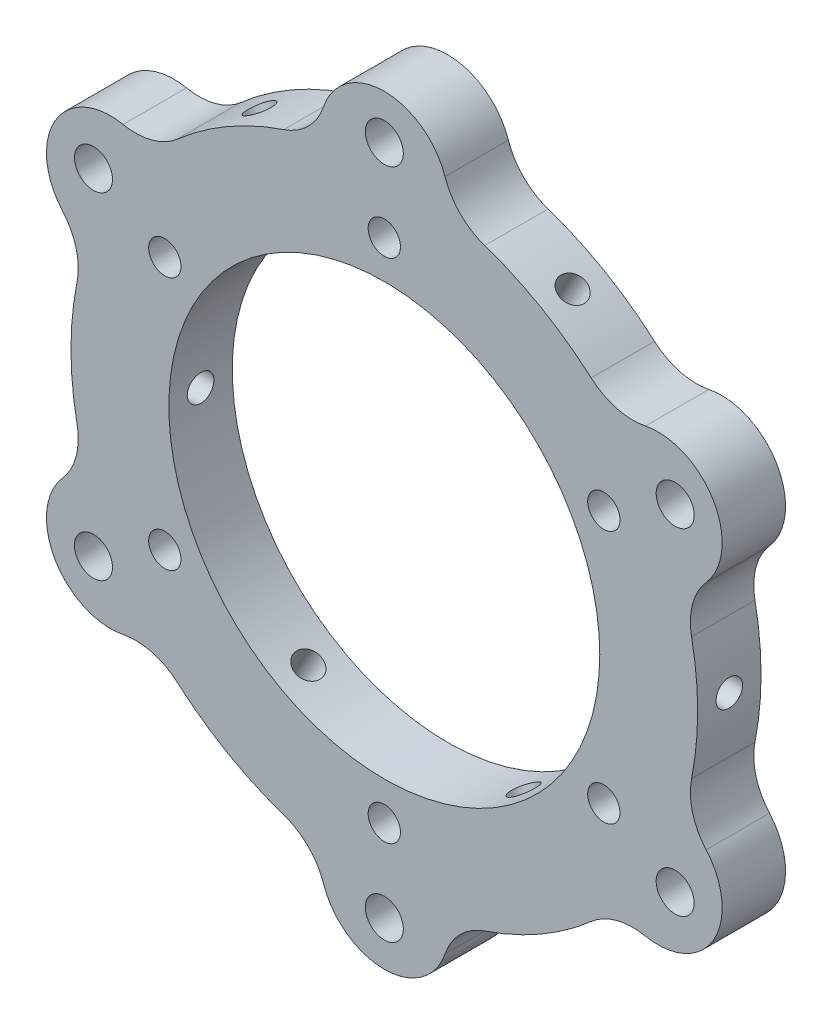
SolidWorks part; units mm, degrees
material "6063-T6"
ref_plane "Front Plane" through (0, 0, 0) normal (0, 0, 1) x (1, 0, 0)
ref_plane "Top Plane" through (0, 0, 0) normal (0, 1, 0) x (1, 0, 0)
ref_plane "Right Plane" through (0, 0, 0) normal (1, 0, 0) x (0, 0, -1)
sketch "Sketch5" plane through (0, 0, 0) normal (0, 1, 0) x (1, 0, 0)
  line L0 (0, -16.5008) -> (0, 15.0181) construction
ref_plane "Plane1" through (0, 0, 0) normal (-0.5, 0.866, 0) x (0, 0, -1)
sketch "Sketch2" plane through (0, 0, 0) normal (0, 0, 1) x (1, 0, 0)
  line L0 (0, 0) -> (0, 53) construction
  line L1 (0, 0) -> (0, 40) construction
  line L2 (0, 0) -> (0, 53) construction
  circle A0 centre (0, 0) radius 34
  circle A1 centre (0, 0) radius 60
  circle A2 centre (0, 53) radius 3
  circle A3 centre (45.8993, 26.5) radius 3
  circle A4 centre (45.8993, -26.5) radius 3
  circle A5 centre (0, -53) radius 3
  circle A6 centre (-45.8993, -26.5) radius 3
  circle A7 centre (-45.8993, 26.5) radius 3
  circle A11 centre (0, 0) radius 53 construction
  circle A12 centre (0, 40) radius 2.55
  circle A13 centre (34.641, 20) radius 2.55
  circle A14 centre (34.641, -20) radius 2.55
  circle A15 centre (0, -40) radius 2.55
  circle A16 centre (-34.641, -20) radius 2.55
  circle A17 centre (-34.641, 20) radius 2.55
  circle A18 centre (0, 0) radius 46.95 construction
  arc A19 (-15.849, 46.8413) -> (15.849, 46.8413) centre (0, 0) ccw
  arc A21 (-9.5776, 53.1206) -> (9.5776, 53.1206) centre (0, 49.8933) cw
  arc A22 (9.5776, 53.1206) -> (15.849, 46.8413) centre (19.0541, 56.3138) ccw
  circle A23 centre (0, 0) radius 49.45 construction
  arc A24 (-9.5776, 53.1206) -> (-15.849, 46.8413) centre (-19.0541, 56.3138) cw
  arc A25 (41.215, 34.8547) -> (50.7926, 18.2658) centre (43.2088, 24.9466) cw
  arc A26 (41.215, 34.8547) -> (32.6413, 37.1463) centre (39.2422, 44.6582) cw
  arc A27 (50.7926, 18.2658) -> (48.4903, 9.695) centre (58.2962, 11.6556) ccw
  arc A28 (50.7926, -18.2658) -> (41.215, -34.8547) centre (43.2088, -24.9466) cw
  arc A29 (50.7926, -18.2658) -> (48.4903, -9.695) centre (58.2962, -11.6556) cw
  arc A30 (41.215, -34.8547) -> (32.6413, -37.1463) centre (39.2422, -44.6582) ccw
  arc A31 (9.5776, -53.1206) -> (-9.5776, -53.1206) centre (0, -49.8933) cw
  arc A32 (9.5776, -53.1206) -> (15.849, -46.8413) centre (19.0541, -56.3138) cw
  arc A33 (-9.5776, -53.1206) -> (-15.849, -46.8413) centre (-19.0541, -56.3138) ccw
  arc A34 (-41.215, -34.8547) -> (-50.7926, -18.2658) centre (-43.2088, -24.9466) cw
  arc A35 (-41.215, -34.8547) -> (-32.6413, -37.1463) centre (-39.2422, -44.6582) cw
  arc A36 (-50.7926, -18.2658) -> (-48.4903, -9.695) centre (-58.2962, -11.6556) ccw
  arc A37 (-50.7926, 18.2658) -> (-41.215, 34.8547) centre (-43.2088, 24.9466) cw
  arc A38 (-50.7926, 18.2658) -> (-48.4903, 9.695) centre (-58.2962, 11.6556) cw
  arc A39 (-41.215, 34.8547) -> (-32.6413, 37.1463) centre (-39.2422, 44.6582) ccw
  point P24 (0, 0)
  point P42 (46.95, 0)
  point P43 (0, 0)
  point P46 (10, 48.4283)
  point P49 (-10, 48.4283)
  point P84 (0, 0)
  dimension "D1" = 6
  dimension "D2" = 68
  dimension "D3" = 120
  dimension "D9" = 5.1
  dimension "D7" = 93.9
  dimension "D12" = 10
  dimension "D10" = 40
  dimension "D4" = 0
  dimension "D11" = 20
  dimension "D8" = 2.5
  dimension "D5" = 6
  dimension "D6" = 6
  dimension "D13" = 6
extrude "Boss-Extrude1" add sketch "Sketch2" along normal blind 10 contours A21 A24 A19 A22 A0 A2 A12 A13 A14 A15 A16 A17 | A39 A37 A38 A19 A7 | A27 A25 A26 A19 A3 | A33 A31 A32 A19 A5 | A36 A34 A35 A19 A6 | A30 A28 A29 A19 A4 region at (52.9238, 23.9788, 0) region at (47.2282, -33.844, 0) region at (5.0355, 56.9038, 0) region at (-5.6959, -57.8232, 0) region at (-47.2282, 33.844, 0) region at (-52.9238, -23.9788, 0)
sketch "Sketch4" plane through (0, 0, 0) normal (-0.5, 0.866, 0) x (0, 0, -1)
  line L0 (0, 0) -> (-10, 0) construction
  line L3 (-16.5008, 0) -> (15.0181, 0) construction
  line L7 (0, -9.695) -> (0, 9.695)
  line L8 (0, 9.695) -> (-10, 9.695)
  line L9 (-10, 9.695) -> (-10, -9.695)
  line L10 (-10, -9.695) -> (0, -9.695)
  line L11 (0, -9.695) -> (0, 9.695)
  line L12 (0, 9.695) -> (-10, 9.695)
  line L13 (-10, 9.695) -> (-10, -9.695)
  line L14 (-10, -9.695) -> (0, -9.695)
  circle A4 centre (-5, 0) radius 2.1
  dimension "D1" = 0
  dimension "D2" = 4.2
extrude "Cut-Extrude1" cut sketch "Sketch4" against normal through all both and the other way through all contours L0 A4 | A4 L0 region at (0.7719, 0.4456, 5) region at (-0.7719, -0.4456, 5)
pattern_circular "CirPattern1" count 6 over 360 about axis through (0, 0, 16.5008) along (0, 0, -1) of "Cut-Extrude1" reverse direction yes
equation "\"D7@Sketch2\"=88.900000+5mm"
